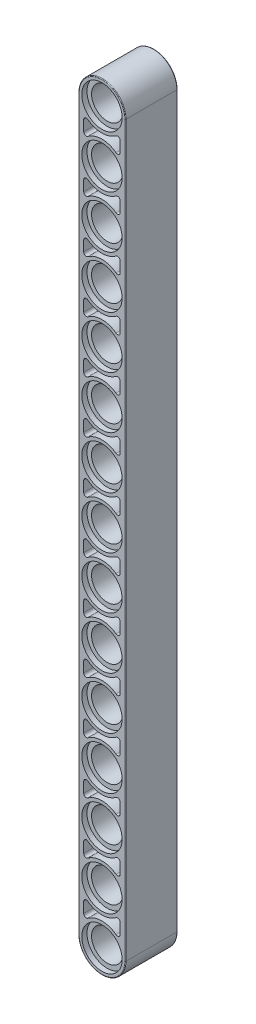
SolidWorks part; units mm, degrees
ref_plane "Front Plane" through (0, 0, 0) normal (0, 0, 1) x (1, 0, 0)
ref_plane "Top Plane" through (0, 0, 0) normal (0, 1, 0) x (1, 0, 0)
ref_plane "Right Plane" through (0, 0, 0) normal (1, 0, 0) x (0, 0, -1)
ref_plane "Plane1" through (0, 0, 4) normal (0, 0, 1) x (1, 0, 0)
sketch "Sketch1" plane through (0, 0, 4) normal (0, 0, 1) x (1, 0, 0)
  line L0 (3.6, -56) -> (3.6, 56)
  line L1 (-3.6, 56) -> (-3.6, -56)
  line L2 (3.6, 0) -> (-3.6, 0) construction
  arc A0 (3.6, 56) -> (-3.6, 56) centre (0, 56) ccw
  arc A1 (-3.6, -56) -> (3.6, -56) centre (0, -56) ccw
  point P6 (0, 0)
  dimension "D2" = 3.6
  dimension "D1" = 112
extrude "Boss-Extrude1" add sketch "Sketch1" against normal blind 8
sketch "Sketch2" plane through (0, 0, 4) normal (0, 0, 1) x (1, 0, 0)
  line L0 (-2.8, -27.2) -> (-2.8, -28.8)
  line L1 (2.8, -28.8) -> (2.8, -27.2)
  arc A0 (2.16, -26.88) -> (-2.16, -26.88) centre (0, -24) cw
  arc A1 (-2.16, -26.88) -> (-2.8, -27.2) centre (-2.4, -27.2) ccw
  arc A2 (-2.8, -28.8) -> (-2.16, -29.12) centre (-2.4, -28.8) ccw
  arc A3 (-2.16, -29.12) -> (2.16, -29.12) centre (0, -32) cw
  arc A4 (2.16, -29.12) -> (2.8, -28.8) centre (2.4, -28.8) ccw
  arc A5 (2.8, -27.2) -> (2.16, -26.88) centre (2.4, -27.2) ccw
extrude "Cut-Extrude1" cut sketch "Sketch2" against normal blind 3.1
sketch "Sketch3" plane through (0, 0, 4) normal (0, 0, 1) x (1, 0, 0)
  line L0 (-2.8, -11.2) -> (-2.8, -12.8)
  line L1 (2.8, -12.8) -> (2.8, -11.2)
  arc A0 (2.16, -10.88) -> (-2.16, -10.88) centre (0, -8) cw
  arc A1 (-2.16, -10.88) -> (-2.8, -11.2) centre (-2.4, -11.2) ccw
  arc A2 (-2.8, -12.8) -> (-2.16, -13.12) centre (-2.4, -12.8) ccw
  arc A3 (-2.16, -13.12) -> (2.16, -13.12) centre (0, -16) cw
  arc A4 (2.16, -13.12) -> (2.8, -12.8) centre (2.4, -12.8) ccw
  arc A5 (2.8, -11.2) -> (2.16, -10.88) centre (2.4, -11.2) ccw
extrude "Cut-Extrude2" cut sketch "Sketch3" against normal blind 3.1
sketch "Sketch4" plane through (0, 0, 4) normal (0, 0, 1) x (1, 0, 0)
  line L0 (-2.8, 4.8) -> (-2.8, 3.2)
  line L1 (2.8, 3.2) -> (2.8, 4.8)
  arc A0 (2.16, 5.12) -> (-2.16, 5.12) centre (0, 8) cw
  arc A1 (-2.16, 5.12) -> (-2.8, 4.8) centre (-2.4, 4.8) ccw
  arc A2 (-2.8, 3.2) -> (-2.16, 2.88) centre (-2.4, 3.2) ccw
  arc A3 (-2.16, 2.88) -> (2.16, 2.88) centre (0, 0) cw
  arc A4 (2.16, 2.88) -> (2.8, 3.2) centre (2.4, 3.2) ccw
  arc A5 (2.8, 4.8) -> (2.16, 5.12) centre (2.4, 4.8) ccw
extrude "Cut-Extrude3" cut sketch "Sketch4" against normal blind 3.1
sketch "Sketch5" plane through (0, 0, 4) normal (0, 0, 1) x (1, 0, 0)
  line L0 (-2.8, 20.8) -> (-2.8, 19.2)
  line L1 (2.8, 19.2) -> (2.8, 20.8)
  arc A0 (2.16, 21.12) -> (-2.16, 21.12) centre (0, 24) cw
  arc A1 (-2.16, 21.12) -> (-2.8, 20.8) centre (-2.4, 20.8) ccw
  arc A2 (-2.8, 19.2) -> (-2.16, 18.88) centre (-2.4, 19.2) ccw
  arc A3 (-2.16, 18.88) -> (2.16, 18.88) centre (0, 16) cw
  arc A4 (2.16, 18.88) -> (2.8, 19.2) centre (2.4, 19.2) ccw
  arc A5 (2.8, 20.8) -> (2.16, 21.12) centre (2.4, 20.8) ccw
extrude "Cut-Extrude4" cut sketch "Sketch5" against normal blind 3.1
sketch "Sketch6" plane through (0, 0, 4) normal (0, 0, 1) x (1, 0, 0)
  line L0 (2.8, 27.2) -> (2.8, 28.8)
  line L1 (-2.8, 28.8) -> (-2.8, 27.2)
  arc A0 (2.8, 28.8) -> (2.16, 29.12) centre (2.4, 28.8) ccw
  arc A1 (2.16, 29.12) -> (-2.16, 29.12) centre (0, 32) cw
  arc A2 (-2.16, 29.12) -> (-2.8, 28.8) centre (-2.4, 28.8) ccw
  arc A3 (-2.8, 27.2) -> (-2.16, 26.88) centre (-2.4, 27.2) ccw
  arc A4 (-2.16, 26.88) -> (2.16, 26.88) centre (0, 24) cw
  arc A5 (2.16, 26.88) -> (2.8, 27.2) centre (2.4, 27.2) ccw
extrude "Cut-Extrude5" cut sketch "Sketch6" against normal blind 3.1
sketch "Sketch7" plane through (0, 0, 4) normal (0, 0, 1) x (1, 0, 0)
  line L0 (-2.8, 12.8) -> (-2.8, 11.2)
  line L1 (2.8, 11.2) -> (2.8, 12.8)
  arc A0 (2.16, 13.12) -> (-2.16, 13.12) centre (0, 16) cw
  arc A1 (-2.16, 13.12) -> (-2.8, 12.8) centre (-2.4, 12.8) ccw
  arc A2 (-2.8, 11.2) -> (-2.16, 10.88) centre (-2.4, 11.2) ccw
  arc A3 (-2.16, 10.88) -> (2.16, 10.88) centre (0, 8) cw
  arc A4 (2.16, 10.88) -> (2.8, 11.2) centre (2.4, 11.2) ccw
  arc A5 (2.8, 12.8) -> (2.16, 13.12) centre (2.4, 12.8) ccw
extrude "Cut-Extrude6" cut sketch "Sketch7" against normal blind 3.1
sketch "Sketch8" plane through (0, 0, 4) normal (0, 0, 1) x (1, 0, 0)
  line L0 (-2.8, -3.2) -> (-2.8, -4.8)
  line L1 (2.8, -4.8) -> (2.8, -3.2)
  arc A0 (2.16, -2.88) -> (-2.16, -2.88) centre (0, 0) cw
  arc A1 (-2.16, -2.88) -> (-2.8, -3.2) centre (-2.4, -3.2) ccw
  arc A2 (-2.8, -4.8) -> (-2.16, -5.12) centre (-2.4, -4.8) ccw
  arc A3 (-2.16, -5.12) -> (2.16, -5.12) centre (0, -8) cw
  arc A4 (2.16, -5.12) -> (2.8, -4.8) centre (2.4, -4.8) ccw
  arc A5 (2.8, -3.2) -> (2.16, -2.88) centre (2.4, -3.2) ccw
extrude "Cut-Extrude7" cut sketch "Sketch8" against normal blind 3.1
sketch "Sketch9" plane through (0, 0, 4) normal (0, 0, 1) x (1, 0, 0)
  line L0 (-2.8, -19.2) -> (-2.8, -20.8)
  line L1 (2.8, -20.8) -> (2.8, -19.2)
  arc A0 (2.16, -18.88) -> (-2.16, -18.88) centre (0, -16) cw
  arc A1 (-2.16, -18.88) -> (-2.8, -19.2) centre (-2.4, -19.2) ccw
  arc A2 (-2.8, -20.8) -> (-2.16, -21.12) centre (-2.4, -20.8) ccw
  arc A3 (-2.16, -21.12) -> (2.16, -21.12) centre (0, -24) cw
  arc A4 (2.16, -21.12) -> (2.8, -20.8) centre (2.4, -20.8) ccw
  arc A5 (2.8, -19.2) -> (2.16, -18.88) centre (2.4, -19.2) ccw
extrude "Cut-Extrude8" cut sketch "Sketch9" against normal blind 3.1
sketch "Sketch10" plane through (0, 0, -4) normal (0, 0, -1) x (-1, 0, 0)
  line L0 (-2.8, -27.2) -> (-2.8, -28.8)
  line L1 (2.8, -28.8) -> (2.8, -27.2)
  arc A0 (-2.8, -28.8) -> (-2.16, -29.12) centre (-2.4, -28.8) ccw
  arc A1 (-2.16, -29.12) -> (2.16, -29.12) centre (0, -32) cw
  arc A2 (2.16, -29.12) -> (2.8, -28.8) centre (2.4, -28.8) ccw
  arc A3 (2.8, -27.2) -> (2.16, -26.88) centre (2.4, -27.2) ccw
  arc A4 (2.16, -26.88) -> (-2.16, -26.88) centre (0, -24) cw
  arc A5 (-2.16, -26.88) -> (-2.8, -27.2) centre (-2.4, -27.2) ccw
extrude "Cut-Extrude9" cut sketch "Sketch10" against normal blind 3.1
sketch "Sketch11" plane through (0, 0, -4) normal (0, 0, -1) x (-1, 0, 0)
  line L0 (-2.8, -19.2) -> (-2.8, -20.8)
  line L1 (2.8, -20.8) -> (2.8, -19.2)
  arc A0 (-2.8, -20.8) -> (-2.16, -21.12) centre (-2.4, -20.8) ccw
  arc A1 (-2.16, -21.12) -> (2.16, -21.12) centre (0, -24) cw
  arc A2 (2.16, -21.12) -> (2.8, -20.8) centre (2.4, -20.8) ccw
  arc A3 (2.8, -19.2) -> (2.16, -18.88) centre (2.4, -19.2) ccw
  arc A4 (2.16, -18.88) -> (-2.16, -18.88) centre (0, -16) cw
  arc A5 (-2.16, -18.88) -> (-2.8, -19.2) centre (-2.4, -19.2) ccw
extrude "Cut-Extrude10" cut sketch "Sketch11" against normal blind 3.1
sketch "Sketch12" plane through (0, 0, -4) normal (0, 0, -1) x (-1, 0, 0)
  line L0 (-2.8, -11.2) -> (-2.8, -12.8)
  line L1 (2.8, -12.8) -> (2.8, -11.2)
  arc A0 (-2.8, -12.8) -> (-2.16, -13.12) centre (-2.4, -12.8) ccw
  arc A1 (-2.16, -13.12) -> (2.16, -13.12) centre (0, -16) cw
  arc A2 (2.16, -13.12) -> (2.8, -12.8) centre (2.4, -12.8) ccw
  arc A3 (2.8, -11.2) -> (2.16, -10.88) centre (2.4, -11.2) ccw
  arc A4 (2.16, -10.88) -> (-2.16, -10.88) centre (0, -8) cw
  arc A5 (-2.16, -10.88) -> (-2.8, -11.2) centre (-2.4, -11.2) ccw
extrude "Cut-Extrude11" cut sketch "Sketch12" against normal blind 3.1
sketch "Sketch13" plane through (0, 0, -4) normal (0, 0, -1) x (-1, 0, 0)
  line L0 (-2.8, -3.2) -> (-2.8, -4.8)
  line L1 (2.8, -4.8) -> (2.8, -3.2)
  arc A0 (-2.8, -4.8) -> (-2.16, -5.12) centre (-2.4, -4.8) ccw
  arc A1 (-2.16, -5.12) -> (2.16, -5.12) centre (0, -8) cw
  arc A2 (2.16, -5.12) -> (2.8, -4.8) centre (2.4, -4.8) ccw
  arc A3 (2.8, -3.2) -> (2.16, -2.88) centre (2.4, -3.2) ccw
  arc A4 (2.16, -2.88) -> (-2.16, -2.88) centre (0, 0) cw
  arc A5 (-2.16, -2.88) -> (-2.8, -3.2) centre (-2.4, -3.2) ccw
extrude "Cut-Extrude12" cut sketch "Sketch13" against normal blind 3.1
sketch "Sketch14" plane through (0, 0, -4) normal (0, 0, -1) x (-1, 0, 0)
  line L0 (-2.8, 4.8) -> (-2.8, 3.2)
  line L1 (2.8, 3.2) -> (2.8, 4.8)
  arc A0 (-2.8, 3.2) -> (-2.16, 2.88) centre (-2.4, 3.2) ccw
  arc A1 (-2.16, 2.88) -> (2.16, 2.88) centre (0, 0) cw
  arc A2 (2.16, 2.88) -> (2.8, 3.2) centre (2.4, 3.2) ccw
  arc A3 (2.8, 4.8) -> (2.16, 5.12) centre (2.4, 4.8) ccw
  arc A4 (2.16, 5.12) -> (-2.16, 5.12) centre (0, 8) cw
  arc A5 (-2.16, 5.12) -> (-2.8, 4.8) centre (-2.4, 4.8) ccw
extrude "Cut-Extrude13" cut sketch "Sketch14" against normal blind 3.1
sketch "Sketch15" plane through (0, 0, -4) normal (0, 0, -1) x (-1, 0, 0)
  line L0 (-2.8, 12.8) -> (-2.8, 11.2)
  line L1 (2.8, 11.2) -> (2.8, 12.8)
  arc A0 (-2.8, 11.2) -> (-2.16, 10.88) centre (-2.4, 11.2) ccw
  arc A1 (-2.16, 10.88) -> (2.16, 10.88) centre (0, 8) cw
  arc A2 (2.16, 10.88) -> (2.8, 11.2) centre (2.4, 11.2) ccw
  arc A3 (2.8, 12.8) -> (2.16, 13.12) centre (2.4, 12.8) ccw
  arc A4 (2.16, 13.12) -> (-2.16, 13.12) centre (0, 16) cw
  arc A5 (-2.16, 13.12) -> (-2.8, 12.8) centre (-2.4, 12.8) ccw
extrude "Cut-Extrude14" cut sketch "Sketch15" against normal blind 3.1
sketch "Sketch16" plane through (0, 0, -4) normal (0, 0, -1) x (-1, 0, 0)
  line L0 (-2.8, 20.8) -> (-2.8, 19.2)
  line L1 (2.8, 19.2) -> (2.8, 20.8)
  arc A0 (-2.8, 19.2) -> (-2.16, 18.88) centre (-2.4, 19.2) ccw
  arc A1 (-2.16, 18.88) -> (2.16, 18.88) centre (0, 16) cw
  arc A2 (2.16, 18.88) -> (2.8, 19.2) centre (2.4, 19.2) ccw
  arc A3 (2.8, 20.8) -> (2.16, 21.12) centre (2.4, 20.8) ccw
  arc A4 (2.16, 21.12) -> (-2.16, 21.12) centre (0, 24) cw
  arc A5 (-2.16, 21.12) -> (-2.8, 20.8) centre (-2.4, 20.8) ccw
extrude "Cut-Extrude15" cut sketch "Sketch16" against normal blind 3.1
sketch "Sketch17" plane through (0, 0, -4) normal (0, 0, -1) x (-1, 0, 0)
  line L0 (-2.8, 28.8) -> (-2.8, 27.2)
  line L1 (2.8, 27.2) -> (2.8, 28.8)
  arc A0 (-2.8, 27.2) -> (-2.16, 26.88) centre (-2.4, 27.2) ccw
  arc A1 (-2.16, 26.88) -> (2.16, 26.88) centre (0, 24) cw
  arc A2 (2.16, 26.88) -> (2.8, 27.2) centre (2.4, 27.2) ccw
  arc A3 (2.8, 28.8) -> (2.16, 29.12) centre (2.4, 28.8) ccw
  arc A4 (2.16, 29.12) -> (-2.16, 29.12) centre (0, 32) cw
  arc A5 (-2.16, 29.12) -> (-2.8, 28.8) centre (-2.4, 28.8) ccw
extrude "Cut-Extrude16" cut sketch "Sketch17" against normal blind 3.1
ref_plane "Plane2" through (0, -32, 0) normal (0, 1, 0) x (1, 0, 0)
sketch "Sketch18" plane through (0, -32, 0) normal (0, 1, 0) x (1, 0, 0)
  line L0 (3.1, 4) -> (0, 4)
  line L1 (0, 4) -> (0, -4)
  line L2 (0, -4) -> (3.1, -4)
  line L3 (3.1, -4) -> (3.1, -3.2)
  line L4 (3.1, -3.2) -> (2.4, -3.2)
  line L5 (2.4, -3.2) -> (2.4, 3.2)
  line L6 (2.4, 3.2) -> (3.1, 3.2)
  line L7 (3.1, 3.2) -> (3.1, 4)
  line L8 (0, 4) -> (0, -4) construction
revolve "Cut-Revolve1" cut sketch "Sketch18" angle 360 about L8 reverse direction yes
ref_plane "Plane3" through (0, -24, 0) normal (0, 1, 0) x (1, 0, 0)
sketch "Sketch19" plane through (0, -24, 0) normal (0, 1, 0) x (1, 0, 0)
  line L0 (3.1, 4) -> (0, 4)
  line L1 (0, 4) -> (0, -4)
  line L2 (0, -4) -> (3.1, -4)
  line L3 (3.1, -4) -> (3.1, -3.2)
  line L4 (3.1, -3.2) -> (2.4, -3.2)
  line L5 (2.4, -3.2) -> (2.4, 3.2)
  line L6 (2.4, 3.2) -> (3.1, 3.2)
  line L7 (3.1, 3.2) -> (3.1, 4)
  line L8 (0, 4) -> (0, -4) construction
revolve "Cut-Revolve2" cut sketch "Sketch19" angle 360 about L8 reverse direction yes
ref_plane "Plane4" through (0, -16, 0) normal (0, 1, 0) x (1, 0, 0)
sketch "Sketch20" plane through (0, -16, 0) normal (0, 1, 0) x (1, 0, 0)
  line L0 (3.1, 4) -> (0, 4)
  line L1 (0, 4) -> (0, -4)
  line L2 (0, -4) -> (3.1, -4)
  line L3 (3.1, -4) -> (3.1, -3.2)
  line L4 (3.1, -3.2) -> (2.4, -3.2)
  line L5 (2.4, -3.2) -> (2.4, 3.2)
  line L6 (2.4, 3.2) -> (3.1, 3.2)
  line L7 (3.1, 3.2) -> (3.1, 4)
  line L8 (0, 4) -> (0, -4) construction
revolve "Cut-Revolve3" cut sketch "Sketch20" angle 360 about L8 reverse direction yes
ref_plane "Plane5" through (0, -8, 0) normal (0, 1, 0) x (1, 0, 0)
sketch "Sketch21" plane through (0, -8, 0) normal (0, 1, 0) x (1, 0, 0)
  line L0 (3.1, 4) -> (0, 4)
  line L1 (0, 4) -> (0, -4)
  line L2 (0, -4) -> (3.1, -4)
  line L3 (3.1, -4) -> (3.1, -3.2)
  line L4 (3.1, -3.2) -> (2.4, -3.2)
  line L5 (2.4, -3.2) -> (2.4, 3.2)
  line L6 (2.4, 3.2) -> (3.1, 3.2)
  line L7 (3.1, 3.2) -> (3.1, 4)
  line L8 (0, 4) -> (0, -4) construction
revolve "Cut-Revolve4" cut sketch "Sketch21" angle 360 about L8 reverse direction yes
sketch "Sketch22" plane through (0, 0, 0) normal (0, 1, 0) x (1, 0, 0)
  line L0 (3.1, 4) -> (0, 4)
  line L1 (0, 4) -> (0, -4)
  line L2 (0, -4) -> (3.1, -4)
  line L3 (3.1, -4) -> (3.1, -3.2)
  line L4 (3.1, -3.2) -> (2.4, -3.2)
  line L5 (2.4, -3.2) -> (2.4, 3.2)
  line L6 (2.4, 3.2) -> (3.1, 3.2)
  line L7 (3.1, 3.2) -> (3.1, 4)
  line L8 (0, 4) -> (0, -4) construction
revolve "Cut-Revolve5" cut sketch "Sketch22" angle 360 about L8 reverse direction yes
ref_plane "Plane6" through (0, 8, 0) normal (0, 1, 0) x (1, 0, 0)
sketch "Sketch23" plane through (0, 8, 0) normal (0, 1, 0) x (1, 0, 0)
  line L0 (3.1, 4) -> (0, 4)
  line L1 (0, 4) -> (0, -4)
  line L2 (0, -4) -> (3.1, -4)
  line L3 (3.1, -4) -> (3.1, -3.2)
  line L4 (3.1, -3.2) -> (2.4, -3.2)
  line L5 (2.4, -3.2) -> (2.4, 3.2)
  line L6 (2.4, 3.2) -> (3.1, 3.2)
  line L7 (3.1, 3.2) -> (3.1, 4)
  line L8 (0, 4) -> (0, -4) construction
revolve "Cut-Revolve6" cut sketch "Sketch23" angle 360 about L8 reverse direction yes
ref_plane "Plane7" through (0, 16, 0) normal (0, 1, 0) x (1, 0, 0)
sketch "Sketch24" plane through (0, 16, 0) normal (0, 1, 0) x (1, 0, 0)
  line L0 (3.1, 4) -> (0, 4)
  line L1 (0, 4) -> (0, -4)
  line L2 (0, -4) -> (3.1, -4)
  line L3 (3.1, -4) -> (3.1, -3.2)
  line L4 (3.1, -3.2) -> (2.4, -3.2)
  line L5 (2.4, -3.2) -> (2.4, 3.2)
  line L6 (2.4, 3.2) -> (3.1, 3.2)
  line L7 (3.1, 3.2) -> (3.1, 4)
  line L8 (0, 4) -> (0, -4) construction
revolve "Cut-Revolve7" cut sketch "Sketch24" angle 360 about L8 reverse direction yes
ref_plane "Plane8" through (0, 24, 0) normal (0, 1, 0) x (1, 0, 0)
sketch "Sketch25" plane through (0, 24, 0) normal (0, 1, 0) x (1, 0, 0)
  line L0 (3.1, 4) -> (0, 4)
  line L1 (0, 4) -> (0, -4)
  line L2 (0, -4) -> (3.1, -4)
  line L3 (3.1, -4) -> (3.1, -3.2)
  line L4 (3.1, -3.2) -> (2.4, -3.2)
  line L5 (2.4, -3.2) -> (2.4, 3.2)
  line L6 (2.4, 3.2) -> (3.1, 3.2)
  line L7 (3.1, 3.2) -> (3.1, 4)
  line L8 (0, 4) -> (0, -4) construction
revolve "Cut-Revolve8" cut sketch "Sketch25" angle 360 about L8 reverse direction yes
ref_plane "Plane9" through (0, 32, 0) normal (0, 1, 0) x (1, 0, 0)
sketch "Sketch26" plane through (0, 32, 0) normal (0, 1, 0) x (1, 0, 0)
  line L0 (3.1, 4) -> (0, 4)
  line L1 (0, 4) -> (0, -4)
  line L2 (0, -4) -> (3.1, -4)
  line L3 (3.1, -4) -> (3.1, -3.2)
  line L4 (3.1, -3.2) -> (2.4, -3.2)
  line L5 (2.4, -3.2) -> (2.4, 3.2)
  line L6 (2.4, 3.2) -> (3.1, 3.2)
  line L7 (3.1, 3.2) -> (3.1, 4)
  line L8 (0, 4) -> (0, -4) construction
revolve "Cut-Revolve9" cut sketch "Sketch26" angle 360 about L8 reverse direction yes
fillet "Fillet1" radius 0.1 8 edges at (0, 59.6, -4) (3.6, 0, -4) (-3.6, 0, -4) (0, -59.6, -4) (-3.6, 0, 4) (0, 59.6, 4) (0, -59.6, 4) (3.6, 0, 4) tangent propagation no
pattern_linear "LPattern1" count 4 spacing 8 along (0, 1, 0) count 12 spacing 8 along (0, -1, 0) of "Cut-Revolve9"
pattern_linear "LPattern2" count 9 spacing 8 along (0, -1, 0) count 6 spacing 8 along (0, 1, 0) of "Cut-Extrude6"
mirror "Mirror1" about plane through (0, 0, 0) normal (0, 0, 1) of "LPattern2"
sketch "Sketch27" plane through (0, 0, -4) normal (0, 0, -1) x (-1, 0, 0)
  line L0 (0, 0) -> (-3.6, 0)
  line L1 (-3.6, -56) -> (-3.6, 56) construction
